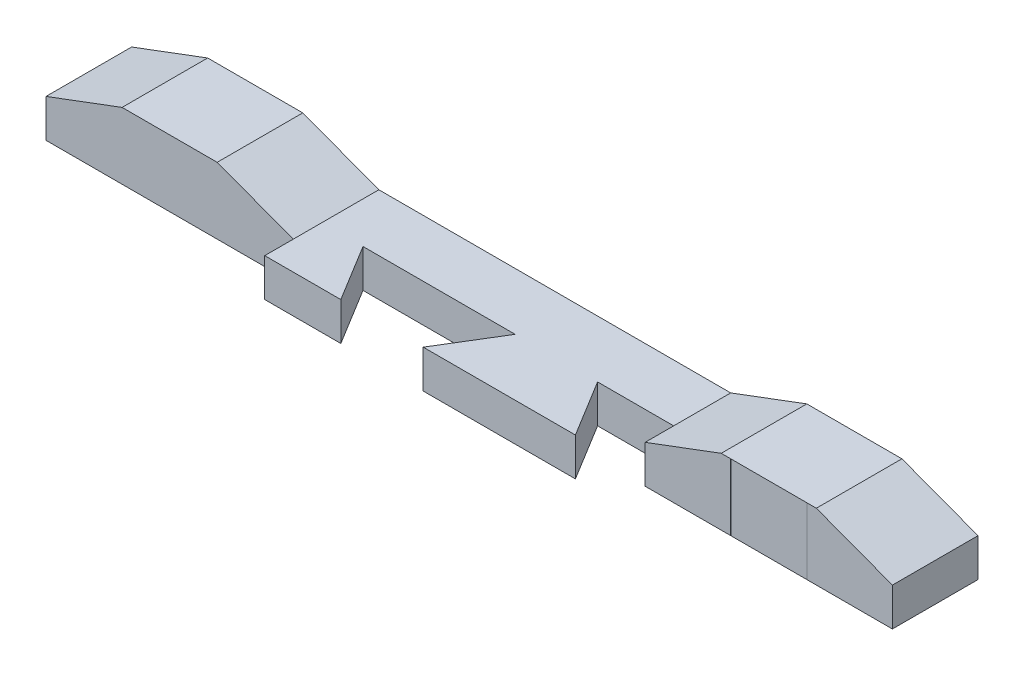
SolidWorks part; units mm, degrees
other "标注1"
sketch "草图3" plane through (-22.25, 4, -10) normal (-0.231, 0.6469, -0.7268) x (-0.9696, -0.2151, 0.1167)
ref_plane "前视基准面" through (0, 0, 0) normal (0, 0, 1) x (1, 0, 0)
ref_plane "上视基准面" through (0, 0, 0) normal (0, 1, 0) x (1, 0, 0)
ref_plane "右视基准面" through (0, 0, 0) normal (1, 0, 0) x (0, 0, -1)
other "Configuration Table"
sketch "草图4" plane through (0, 0, 0) normal (0, 0, 1) x (1, 0, 0)
  line L6 (8.5, -1.5) -> (17.75, -1.5)
  line L11 (17.75, -1.5) -> (17.75, -3.5)
  line L16 (17.75, -3.5) -> (-4.5, -3.5)
  line L17 (-4.5, -3.5) -> (-4.5, -1.5)
  line L22 (0, 0) -> (4, 0)
  line L26 (4, 0) -> (4.5, 0)
  line L27 (4.5, 0) -> (8.5, -1.5)
  line L28 (0, 0) -> (-0.5, 0)
  line L29 (-0.5, 0) -> (-4.5, -1.5)
  dimension "D2" = 9.25
  dimension "D4" = 0.5
  dimension "D5" = 2
  dimension "D7" = 4
  dimension "D8" = 1.5
  dimension "D9" = 4
  dimension "D10" = 22.25
extrude "凸台-拉伸1" add sketch "草图4" along normal blind 4 contours L28 L29 L17 L16 L11 L6 L27 L26 region at (5.5485, -2.1185, 0)
mirror "镜向1" about plane through (0, 0, 4) normal (0, 0, 1) of bodies 202 203
mirror "镜向2" about plane through (17.75, 0, 4) normal (1, 0, 0) of bodies 204
sketch "草图6" plane through (0, -1.5, 0) normal (0, 1, 0) x (1, 0, 0)
  line L1 (10.6667, -2.5) -> (12.5, -5.5)
  line L4 (10.6667, -2.5) -> (18.6667, -2.5)
  line L5 (18.6667, -2.5) -> (16.8333, -5.5)
  line L6 (16.8333, -5.5) -> (24.8333, -5.5)
  line L7 (24.8333, -5.5) -> (23, -2.5)
  line L8 (23, -2.5) -> (27, -2.5)
  line L9 (12.5, -5.5) -> (8.5, -5.5)
  line L10 (8.5, -8) -> (8.5, 0) construction
  line L15 (-4.5, -4) -> (8.5, -4)
  line L19 (27, -8) -> (27, 0) construction
  line L21 (-4.5, -8) -> (-4.5, 0) construction
  line L22 (8.5, -4) -> (8.5, -5.5)
  line L23 (27, -2.5) -> (27, -4)
  line L24 (27, -4) -> (40, -4)
  line L25 (40, -8) -> (40, 0) construction
  line L26 (-4.5, -4) -> (-4.5, 0)
  line L27 (-4.5, 0) -> (40, 0)
  line L28 (40, 0) -> (40, -4)
  line L29 (-4.5, -4) -> (-4.5, -8)
  line L30 (-4.5, -8) -> (40, -8)
  line L31 (40, -8) -> (40, -4)
  line M2 (8.5, 0) -> (8.5, -8)
  line M3 (8.5, -8) -> (27, -8)
  line M4 (27, -8) -> (27, 0)
  dimension "D1" = 3
  dimension "D2" = 8
  dimension "D3" = 4
extrude "切除-拉伸6" cut sketch "草图6" against normal through all both and the other way through all contours L29 L30 L15 M2 | L8 L7 L6 L5 L4 L1 L9 M2 M3 M4 | L30 L31 L24 M4 region at (17.937, -1.5, 5.663) region at (2, -1.5, 6) region at (33.5, -1.5, 6)
sketch "草图7" plane through (0, 0, 0) normal (0, 0, -1) x (-1, 0, 0)
  line L18 (0.5, 0) -> (-4.5, 0)
  line L23 (-4.5, 0) -> (-8.5, -1.5)
  line L24 (-8.5, -1.5) -> (-27, -1.5)
  line L25 (-27, -1.5) -> (-31, 0)
  line L26 (-31, 0) -> (-36, 0)
  line L31 (-36, 0) -> (-40, -1.5)
  line L32 (-40, -1.5) -> (-40, -3.5)
  line L33 (-40, -3.5) -> (4.5, -3.5)
  line L34 (4.5, -3.5) -> (4.5, -1.5)
  line L35 (4.5, -1.5) -> (0.5, 0)
  line L36 (0.5, 0) -> (-4.5, 0)
  line L41 (-4.5, 0) -> (-8.5, -1.5)
  line L42 (-8.5, -1.5) -> (-27, -1.5)
  line L43 (-27, -1.5) -> (-31, 0)
  line L44 (-31, 0) -> (-36, 0)
  line L49 (-36, 0) -> (-40, -1.5)
  line L50 (-40, -1.5) -> (-40, -3.5)
  line L51 (-40, -3.5) -> (4.5, -3.5)
  line L52 (4.5, -3.5) -> (4.5, -1.5)
  line L53 (4.5, -1.5) -> (0.5, 0)
  dimension "D1" = 0
extrude "凸台-拉伸2" add sketch "草图7" along normal blind 0.5
sketch "草图8" plane through (0, 0, 4) normal (0, 0, 1) x (1, 0, 0)
  line L0 (31, 0) -> (31.5, 0) construction
  line L1 (31, 0) -> (36, 0) construction
  line L2 (31.5, 0) -> (31.5, -3.5)
  line L3 (27, -3.5) -> (40, -3.5) construction
  line L4 (31.5, -3.5) -> (35.5, -3.5)
  line L5 (35.5, -3.5) -> (35.5, 0)
  line L6 (35.5, 0) -> (31.5, 0)
  line L7 (35.5, 0) -> (36, 0) construction
  dimension "D1" = 4
extrude "切除-拉伸7" cut sketch "草图8" against normal blind 0.001
